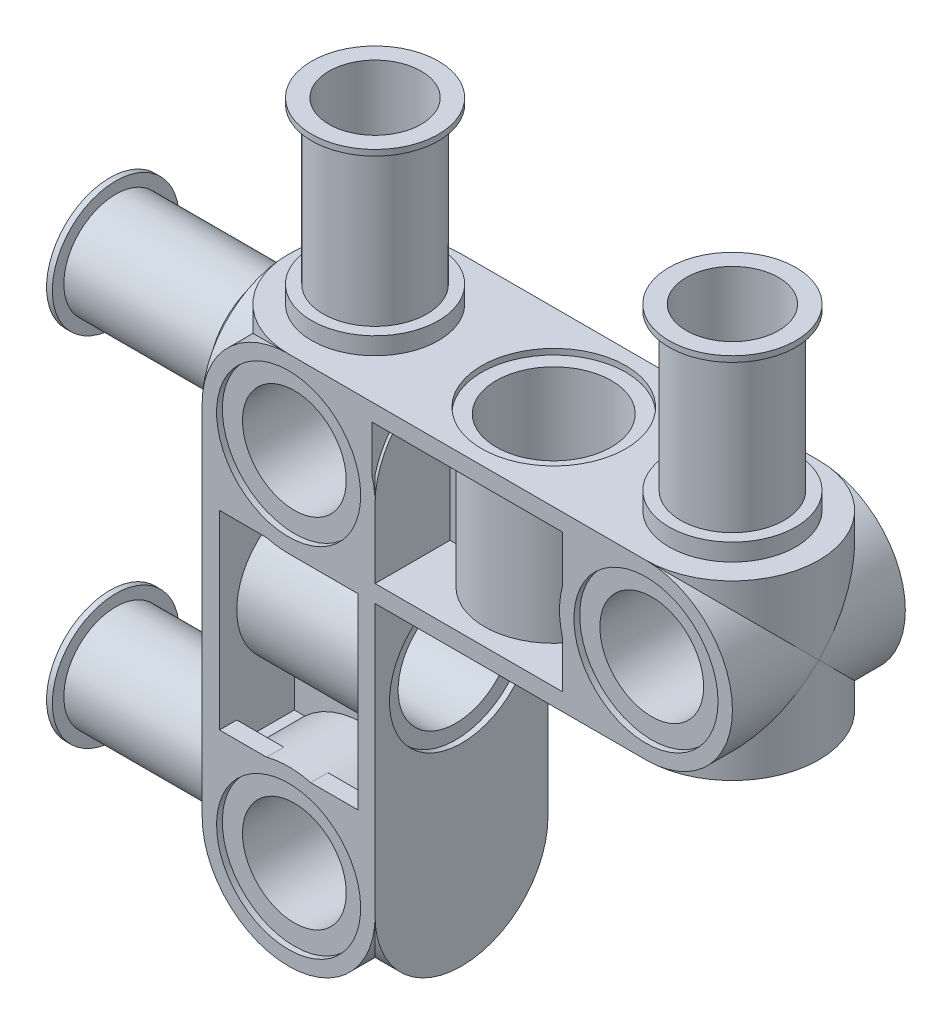
SolidWorks part; units mm, degrees
material "PVC Rigid"
ref_plane "Front Plane" through (0, 0, 0) normal (0, 0, 1) x (1, 0, 0)
ref_plane "Top Plane" through (0, 0, 0) normal (0, 1, 0) x (1, 0, 0)
ref_plane "Right Plane" through (0, 0, 0) normal (1, 0, 0) x (0, 0, -1)
sketch "Sketch1" plane through (0, 0, 0) normal (0, 1, 0) x (1, 0, 0)
  line L0 (-19.2625, 0) -> (26.4221, 0) construction
  line L1 (-7.874, 3.81) -> (7.874, 3.81)
  line L2 (0, 0) -> (0, 11.754) construction
  line L3 (7.874, -3.81) -> (-7.874, -3.81)
  circle A0 centre (-7.874, 0) radius 2.54 construction
  circle A1 centre (0, 0) radius 2.54 construction
  circle A2 centre (7.874, 0) radius 2.54 construction
  arc A3 (7.874, -3.81) -> (7.874, 3.81) centre (7.874, 0) ccw
  arc A4 (-7.874, 3.81) -> (-7.874, -3.81) centre (-7.874, 0) ccw
  dimension "D3" = 5.08
  dimension "D4" = 7.62
  dimension "D1" = 7.874
  dimension "D2" = 7.874
extrude "Extrude1" add sketch "Sketch1" along normal blind 3.81
sketch "Sketch2" plane through (0, 0, 0) normal (0, -1, 0) x (1, 0, 0)
  circle A0 centre (0, 0) radius 2.794
  dimension "D1" = 5.588
extrude "Cut-Extrude1" cut sketch "Sketch2" against normal blind 0.254
sketch "Sketch3" plane through (0, 0, 0) normal (0, -1, 0) x (1, 0, 0)
  circle A0 centre (7.874, 0) radius 2.794
  circle A1 centre (-7.874, 0) radius 2.794
  arc A2 (-7.874, 3.81) -> (-7.874, -3.81) centre (-7.874, 0) ccw construction
  arc A3 (7.874, -3.81) -> (7.874, 3.81) centre (7.874, 0) ccw construction
  dimension "D1" = 5.588
extrude "Extrude2" add sketch "Sketch3" along normal blind 0.762
sketch "Sketch5" plane through (0, -0.762, 0) normal (0, -1, 0) x (1, 0, 0)
  circle A0 centre (7.874, 0) radius 2.794 construction
  circle A1 centre (7.874, 0) radius 2.286
  circle A2 centre (-7.874, 0) radius 2.794 construction
  circle A3 centre (7.874, 0) radius 2.032
  circle A4 centre (-7.874, 0) radius 2.286
  circle A8 centre (-7.874, 0) radius 2.032
  dimension "D2" = 4.572
  dimension "D1" = 4.064
extrude "Extrude4" add sketch "Sketch5" along normal blind 7.112
sketch "Sketch6" plane through (0, -7.874, 0) normal (0, -1, 0) x (1, 0, 0)
  circle A1 centre (-7.874, 0) radius 2.032 construction
  circle A3 centre (7.874, 0) radius 2.032 construction
  circle A4 centre (-7.874, 0) radius 2.794 construction
  circle A5 centre (7.874, 0) radius 2.794 construction
  circle A6 centre (-7.874, 0) radius 2.794
  circle A7 centre (7.874, 0) radius 2.794
  circle A8 centre (7.874, 0) radius 2.032
  circle A9 centre (-7.874, 0) radius 2.032
extrude "Extrude5" add sketch "Sketch6" against normal blind 0.254
sketch "Sketch7" plane through (0, 0, -3.81) normal (0, 0, -1) x (-1, 0, 0)
  line L0 (-7.874, 3.81) -> (7.874, 3.81) construction
  line L2 (-7.874, 0) -> (7.874, 0) construction
  line L3 (-7.874, 0) -> (7.874, 0)
  line L4 (-7.874, 3.81) -> (7.874, 3.81)
  line L5 (-7.874, 3.81) -> (-11.684, 3.81)
  line L6 (7.874, 3.81) -> (11.684, 3.81)
  arc A0 (-11.684, 3.81) -> (-7.874, 0) centre (-7.874, 3.81) ccw
  arc A1 (7.874, 0) -> (11.684, 3.81) centre (7.874, 3.81) ccw
extrude "Extrude6" add sketch "Sketch7" against normal blind 7.62
sketch "Sketch8" plane through (0, 3.81, 0) normal (0, 1, 0) x (1, 0, 0)
  circle A0 centre (-7.874, 0) radius 2.54 construction
  circle A1 centre (0, 0) radius 2.54 construction
  circle A2 centre (7.874, 0) radius 2.54 construction
  circle A3 centre (-7.874, 0) radius 2.54 construction
  circle A4 centre (0, 0) radius 2.54
  circle A5 centre (7.874, 0) radius 2.54 construction
extrude "Cut-Extrude2" cut sketch "Sketch8" against normal blind 3.556
sketch "Sketch9" plane through (0, 0, 3.81) normal (0, 0, 1) x (1, 0, 0)
  circle A0 centre (7.874, 3.81) radius 2.286
  circle A1 centre (-7.874, 3.81) radius 2.286
  dimension "D1" = 4.572
extrude "Cut-Extrude3" cut sketch "Sketch9" against normal through all
sketch "Sketch10" plane through (0, 0, 3.81) normal (0, 0, 1) x (1, 0, 0)
  circle A0 centre (7.874, 3.81) radius 3.175
  circle A1 centre (-7.874, 3.81) radius 3.175
  dimension "D1" = 6.35
extrude "Cut-Extrude4" cut sketch "Sketch10" against normal blind 0.254
mirror "Mirror2" about plane through (0, 0, 0) normal (0, 0, 1) of "Cut-Extrude4"
sketch "Sketch11" plane through (0, 3.81, 0) normal (0, 1, 0) x (1, 0, 0)
  line L0 (-5.08, -0.508) -> (-5.08, -3.048)
  line L1 (5.08, 0.508) -> (5.08, 3.048)
  line L2 (5.08, -3.048) -> (5.08, -0.508)
  line L23 (4.699, 3.81) -> (-4.699, 3.81) construction
  line L24 (-5.809, 0) -> (6.5071, 0) construction
  line L25 (-5.08, 0.508) -> (-3.0054, 0.508)
  line L26 (-5.809, 0.508) -> (6.5071, 0.508) construction
  line L27 (-5.08, -0.508) -> (-3.0054, -0.508)
  line L28 (-5.809, -0.508) -> (6.5071, -0.508) construction
  line L29 (-4.699, -3.81) -> (4.699, -3.81) construction
  line L30 (-4.191, -3.81) -> (4.191, -3.81)
  line L31 (3.0054, -0.508) -> (5.08, -0.508)
  line L32 (-4.191, -3.048) -> (-4.191, -3.302)
  line L33 (-4.191, -3.302) -> (4.191, -3.302)
  line L34 (4.191, -3.302) -> (4.191, -3.048)
  line L35 (4.191, -3.048) -> (5.08, -3.048)
  line L36 (5.08, -3.048) -> (5.08, 3.048)
  line L37 (4.191, 3.302) -> (-4.191, 3.302)
  line L38 (4.191, 3.81) -> (-4.191, 3.81)
  line L39 (-4.191, 3.302) -> (-4.191, 3.048)
  line L40 (-5.08, 3.048) -> (-5.08, -3.048)
  line L41 (-5.08, -3.048) -> (-4.191, -3.048)
  line L42 (-4.191, -3.048) -> (-4.191, -3.81)
  line L43 (3.0054, 0.508) -> (5.08, 0.508)
  line L44 (4.191, -3.81) -> (4.191, -3.048)
  line L45 (4.191, -3.048) -> (5.08, -3.048)
  line L47 (-4.191, 3.81) -> (-4.191, 3.048)
  line L49 (-4.191, 3.048) -> (-5.08, 3.048)
  line L50 (-5.08, 3.048) -> (-5.08, 0.508)
  line L51 (-5.08, -3.048) -> (-4.191, -3.048)
  line L65 (-4.191, 3.048) -> (-5.08, 3.048)
  line L70 (5.08, 3.048) -> (4.191, 3.048)
  line L71 (5.08, 3.048) -> (4.191, 3.048)
  line L72 (4.191, 3.048) -> (4.191, 3.302)
  line L73 (4.191, 3.048) -> (4.191, 3.81)
  circle A5 centre (0, 0) radius 3.048
  arc A6 (-3.0054, -0.508) -> (3.0054, -0.508) centre (0, 0) ccw
  arc A8 (3.0054, 0.508) -> (-3.0054, 0.508) centre (0, 0) ccw
  dimension "D1" = 0.508
  dimension "D2" = 0.508
  dimension "D3" = 0.508
  dimension "D4" = 0.508
extrude "Cut-Extrude6" cut sketch "Sketch11" against normal blind 3.048
sketch "Sketch13" plane through (0, 0.254, 0) normal (0, 1, 0) x (1, 0, 0)
  circle A1 centre (0, 0) radius 2.54
  circle A2 centre (0, 0) radius 2.54
  dimension "D1" = 0
extrude "Cut-Extrude7" cut sketch "Sketch13" against normal through all
sketch "Sketch14" plane through (0, 0, 0) normal (0, -1, 0) x (1, 0, 0)
  circle A0 centre (0, 0) radius 3.175
  dimension "D1" = 6.35
extrude "Cut-Extrude8" cut sketch "Sketch14" against normal blind 0.254
sketch "Sketch17" plane through (0, 0, 3.81) normal (0, 0, 1) x (1, 0, 0)
  line L0 (-4.064, 3.81) -> (-4.699, 3.81)
  line L1 (-11.049, 3.81) -> (-11.684, 3.81)
  arc A0 (-11.684, 3.81) -> (-4.064, 3.81) centre (-7.874, 3.81) ccw
  arc A1 (-11.049, 3.81) -> (-4.699, 3.81) centre (-7.874, 3.81) ccw construction
  arc A2 (-11.049, 3.81) -> (-4.699, 3.81) centre (-7.874, 3.81) ccw
  dimension "D1" = 3.81
extrude "Extrude8" add sketch "Sketch17" against normal blind 7.112
mirror "Mirror3" about plane through (0, 0, 0) normal (1, 0, 0) of "Extrude8"
mirror "Mirror1" about plane through (-7.874, 3.81, 0) normal (0, 1, 0) of bodies 118 111
sketch "Sketch18" plane through (0, 0, 3.81) normal (0, 0, 1) x (1, 0, 0)
  line L0 (-14.1345, 0) -> (15.6326, 0)
extrude "Extrude10" cut sketch "Sketch18" against normal through all and the other way through all flip side to cut
pattern_circular "CirPattern1" count 2 every 90 about axis through (-7.874, 3.81, 3.556) along (0, 0, -1) of bodies 121
sketch "Sketch19" plane through (0, 0, 3.81) normal (0, 0, 1) x (1, 0, 0)
  point P0 (-7.874, 3.81)
ref_plane "Plane1" through (-7.874, 0, 0) normal (1, 0, 0) x (0, 0, -1)
mirror "Mirror4" about plane through (-7.874, 0, 0) normal (1, 0, 0) of bodies 122
delete or keep bodies "Body-Delete1" type delete bodies bodies 122
combine bodies "Combine1" operation type add bodies to combine 121 123
